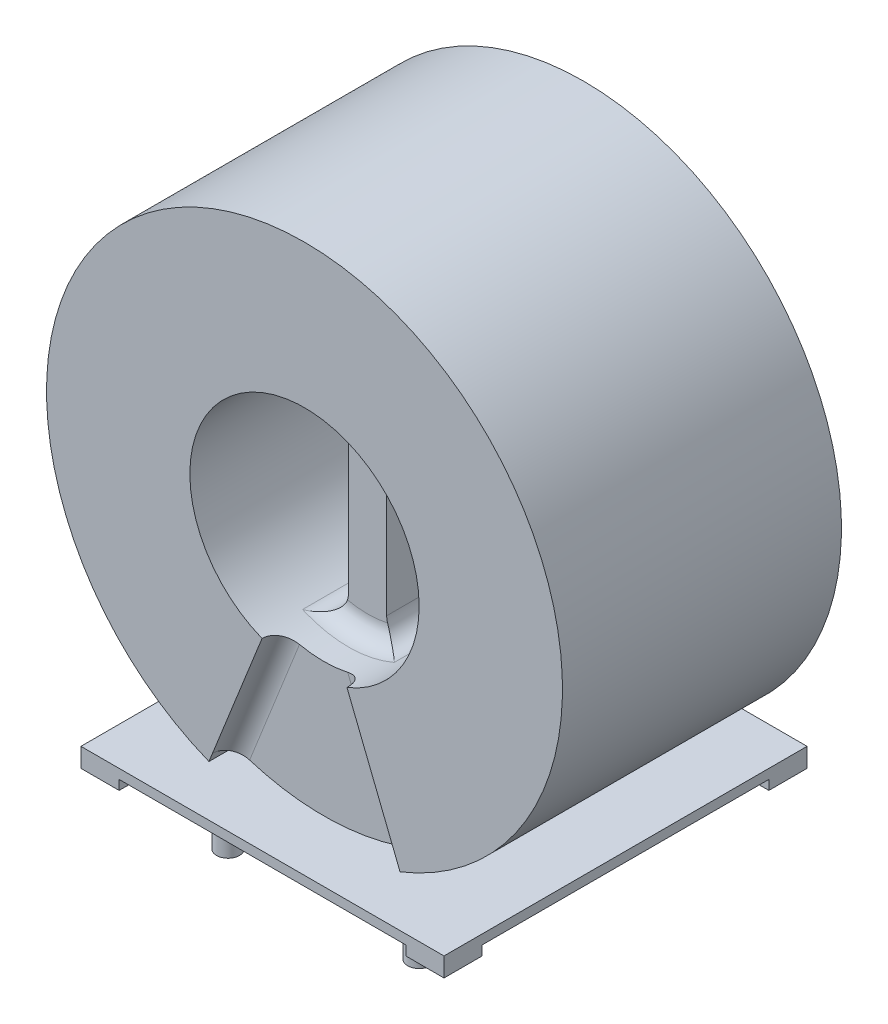
SolidWorks part; units mm, degrees
ref_plane "Front Plane" through (0, 0, 0) normal (0, 0, 1) x (1, 0, 0)
ref_plane "Top Plane" through (0, 0, 0) normal (0, 1, 0) x (1, 0, 0)
ref_plane "Right Plane" through (0, 0, 0) normal (1, 0, 0) x (0, 0, -1)
sketch "Sketch1" plane through (0, 0, 0) normal (0, 1, 0) x (1, 0, 0)
  line L0 (0, 0) -> (19, 0)
  line L1 (19, 0) -> (19, 19)
  line L2 (19, 19) -> (0, 19)
  line L3 (0, 19) -> (0, 0)
  line L4 (14.5, 3.2) -> (14.5, 15.8) construction
  line L5 (14.5, 15.8) -> (4.5, 15.8) construction
  line L6 (4.5, 15.8) -> (4.5, 3.2) construction
  line L8 (0, 19) -> (2, 19)
  line L9 (0, 19) -> (0, 17)
  line L10 (0, 17) -> (2, 17)
  line L11 (2, 19) -> (2, 17)
  line L12 (19, 19) -> (17, 19)
  line L13 (19, 19) -> (19, 17)
  line L14 (19, 17) -> (17, 17)
  line L15 (17, 19) -> (17, 17)
  line L16 (19, 0) -> (17, 0)
  line L17 (19, 0) -> (19, 2)
  line L18 (19, 2) -> (17, 2)
  line L19 (17, 0) -> (17, 2)
  line L20 (0, 0) -> (2, 0)
  line L21 (0, 0) -> (0, 2)
  line L22 (0, 2) -> (2, 2)
  line L23 (2, 0) -> (2, 2)
  circle A0 centre (4.5, 15.8) radius 0.6
  circle A1 centre (4.5, 3.2) radius 0.6
  circle A2 centre (14.5, 3.2) radius 0.6
  circle A3 centre (14.5, 15.8) radius 0.6
  dimension "D5" = 1.2
  dimension "D1" = 19
  dimension "D2" = 19
  dimension "D3" = 3.2
  dimension "D4" = 4.5
  dimension "D6" = 12.6
  dimension "D7" = 10
  dimension "D8" = 2
extrude "Boss-Extrude1" add sketch "Sketch1" against normal blind 0.5 contours L11 L2 L3 L10 | L19 L0 L1 L18 | L2 L15 L14 L1 | L21 L22 L23 L20 region at (18, 0, -1) region at (1, 0, -18) region at (18, 0, -18)
extrude "Boss-Extrude2" add sketch "Sketch1<4>" against normal blind 3.5 separate body contours A1 | A2 | A3 | A0 region at (4.5, 0, -3.2) region at (14.5, 0, -3.2) region at (14.5, 0, -15.8)
sketch "Sketch1<4>" plane through (0, 0, 0) normal (0, 1, 0) x (1, 0, 0) same geometry as "Sketch1"
extrude "Boss-Extrude3" add sketch "Sketch1<5>" along normal blind 0.5 contours L23 L0 L19 L18 L1 L14 L15 L2 L11 L10 L3 L22 A3 A2 A1 A0 | L0 L23 L22 L3 | A1 | A0 | L11 L2 L3 L10 | A3 | L2 L15 L14 L1 | A2 | L19 L0 L1 L18 region at (1, 0, -1) region at (9.5, 0, -9.5) region at (18, 0, -1) region at (1, 0, -18) region at (18, 0, -18) region at (4.5, 0, -15.8) region at (4.5, 0, -3.2) region at (14.5, 0, -3.2) region at (14.5, 0, -15.8)
sketch "Sketch1<5>" plane through (0, 0, 0) normal (0, 1, 0) x (1, 0, 0) same geometry as "Sketch1"
ref_plane "Plane1" through (0, 0, -9.5) normal (0, 0, 1) x (1, 0, 0)
sketch "Sketch2" plane through (0, 0, -9.5) normal (0, 0, 1) x (1, 0, 0)
  line L0 (0, 0) -> (19, 0) construction
  line L1 (9.5, 0) -> (9.5, 0.5) construction
  line L2 (0, 0.5) -> (19, 0.5) construction
  line L3 (9.5, 0) -> (9.5, 0.5) construction
  line L4 (10.5, 0) -> (10.5, 0.5385)
  line L5 (8.5, 0) -> (8.5, 0.5385)
  line L6 (10.5, 7.5839) -> (10.5, 19.4161)
  line L7 (10.5, -986.5) -> (10.5, 50013.5) construction
  line L8 (9.5, 7.5) -> (9.5, 13.5) construction
  line L9 (9.5, -986.5) -> (9.5, 50013.5) construction
  line L10 (9.5, 7.5) -> (9.5, 19.5) construction
  line L11 (8.5, -986.5) -> (8.5, 50013.5) construction
  line L12 (8.5, 7.5839) -> (8.5, 19.4161)
  circle A0 centre (9.5, 13.5) radius 13
  circle A1 centre (9.5, 13.5) radius 6
  dimension "D2" = 12
  dimension "D1" = 13.5
  dimension "D3" = 1
  dimension "D4" = 1
extrude "Boss-Extrude4" add sketch "Sketch2" along normal blind 6.3 separate body contours A0 A1 region at (18.7696, 4.918, -9.5)
extrude "Boss-Extrude5" add sketch "Sketch2<3>" along normal blind 4 contours L6 A1 L12 region at (9.5, 13.5, -9.5)
sketch "Sketch2<3>" plane through (0, 0, -9.5) normal (0, 0, 1) x (1, 0, 0) same geometry as "Sketch2"
fillet "Fillet1" radius 1 4 edges at (8.5, 19.4161, -7.5) (10.5, 19.4161, -7.5) (10.5, 7.5839, -7.5) (8.5, 7.5839, -7.5)
mirror "Mirror2" about plane through (0, 0, -9.5) normal (0, 0, 1) of bodies 111
fillet "Fillet2" radius 1 4 edges at (9.5, 19.5, -5.5) (9.5, 7.5, -5.5) (9.5, 7.5, -13.5) (9.5, 19.5, -13.5)
sketch "Sketch4" plane through (0, 0, -15.8) normal (0, 0, -1) x (-1, 0, 0)
  line L0 (-9.5, 13.5) -> (-14.5, 0.9601)
  line L1 (-9.5, 13.5) -> (-4.5, 0.9601)
  circle A0 centre (-9.5, 13.5) radius 13.5
  circle M2 centre (-9.5, 13.5) radius 6
  circle M3 centre (-9.5, 13.5) radius 13
  dimension "D1" = 27
  dimension "D2" = 5
  dimension "D3" = 5
extrude "Boss-Extrude7" add sketch "Sketch4" against normal offset from surface 1 and the other way blind 1 contours L1 L0 M2 M3 | L1 A0 L0 M3 region at (13.354, 4.8094, -15.8) region at (14.7558, 1.3312, -15.8) up to face at (15.5, 13.5, -3.2) offset beyond the face yes
fillet "Fillet3" radius 1 4 edges at (5.9815, 4.6756, -15.8) (13.0185, 4.6756, -15.8) (13.0185, 4.6756, -3.2) (5.9815, 4.6756, -3.2)
